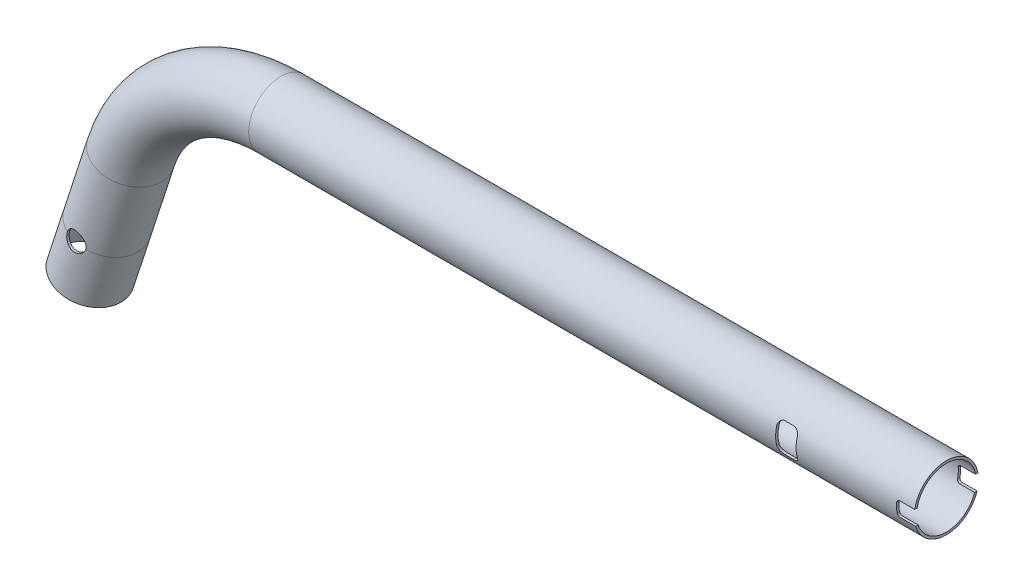
SolidWorks part; units mm, degrees
ref_plane "Front Plane" through (0, 0, 0) normal (0, 0, 1) x (1, 0, 0)
ref_plane "Top Plane" through (0, 0, 0) normal (0, 1, 0) x (1, 0, 0)
ref_plane "Right Plane" through (0, 0, 0) normal (1, 0, 0) x (0, 0, -1)
sketch "Sketch1" plane through (0, 0, 0) normal (0, 0, 1) x (1, 0, 0)
  line L0 (-91.9783, 0) -> (91.9783, 0)
  line L1 (-143.3354, -37.3131) -> (-151.4217, -62.2)
  line L2 (91.9783, 0) -> (135.9783, 0)
  line L3 (-151.4217, -62.2) -> (-157.2052, -80)
  arc A0 (-91.9783, 0) -> (-143.3354, -37.3131) centre (-91.9783, -54) ccw
  point P4 (0, 0)
  point P10 (-151.4217, -62.2)
  dimension "D2" = 54
  dimension "D1" = 72
  dimension "D3" = 62.2
  dimension "D4" = 243.4
  dimension "D5" = 80
  dimension "D6" = 72
  dimension "D7" = 44
ref_plane "Plane1" through (91.9783, 0, 0) normal (1, 0, 0) x (0, 0, -1)
sketch "Sketch3" plane through (91.9783, 0, 0) normal (1, 0, 0) x (0, 0, -1)
  circle A0 centre (0, 0) radius 11
  circle A1 centre (0, 0) radius 10.2
  dimension "D1" = 0.8
  dimension "D2" = 22
sweep "Sweep2" add profiles "Sketch3" path "Sketch1"
ref_axis "Axis1" through (135.9783, 0, 0) along (-1, 0, 0)
ref_axis "Axis2" through (-141.3374, -31.1639, 0) along (-0.309, -0.9511, 0)
sketch "Sketch4" plane through (0, 0, 0) normal (0, 0, 1) x (1, 0, 0)
  line L0 (-161.8833, -58.8008) -> (-140.96, -65.5992) construction
  line L1 (91.9783, -101.4635) -> (91.9783, 101.4635) construction
  line L2 (135.9783, 0) -> (91.9783, 0) construction
  line L3 (135.9783, -11) -> (135.9783, 11) construction
  line L4 (135.9783, 0) -> (-91.9783, 0) construction
  line L6 (90.4783, -5) -> (93.4783, -5)
  line L7 (88.4783, -3) -> (88.4783, 3)
  line L8 (90.4783, 5) -> (93.4783, 5)
  line L9 (95.4783, -3) -> (95.4783, 3)
  line L10 (88.4783, -5) -> (95.4783, 5) construction
  line L11 (88.4783, 5) -> (95.4783, -5) construction
  circle A0 centre (-151.4217, -62.2) radius 3.3
  arc A1 (90.4783, -5) -> (88.4783, -3) centre (90.4783, -3) cw
  arc A2 (95.4783, -3) -> (93.4783, -5) centre (93.4783, -3) cw
  arc A3 (93.4783, 5) -> (95.4783, 3) centre (93.4783, 3) cw
  arc A4 (90.4783, 5) -> (88.4783, 3) centre (90.4783, 3) ccw
  dimension "D1" = 44
  dimension "D4" = 2
  dimension "D6" = 6.6
  dimension "D2" = 7
  dimension "D3" = 10
extrude "Cut-Extrude1" cut sketch "Sketch4" along normal up to next
sketch "Sketch5" plane through (0, 0, 0) normal (0, 0, 1) x (1, 0, 0)
  line L0 (-161.1224, -59.048) -> (-141.7209, -65.352) construction
  circle A0 centre (-151.4217, -62.2) radius 3.3
extrude "Cut-Extrude2" cut sketch "Sketch5" against normal through all
sketch "Sketch6" plane through (0, 0, 0) normal (0, 0, 1) x (1, 0, 0)
  line L0 (135.9783, 1.95) -> (135.9783, -3.25)
  line L1 (135.9783, -11) -> (135.9783, 11) construction
  line L2 (135.9783, -3.25) -> (130.8783, -3.25)
  line L3 (129.8783, -2.25) -> (129.8783, 0.95)
  line L4 (130.8783, 1.95) -> (135.9783, 1.95)
  arc A0 (129.8783, -2.25) -> (130.8783, -3.25) centre (130.8783, -2.25) ccw
  arc A1 (130.8783, 1.95) -> (129.8783, 0.95) centre (130.8783, 0.95) ccw
  point P5 (135.9783, -0.65)
  point P9 (129.8783, -3.25)
  dimension "D3" = 1
  dimension "D1" = 5.2
  dimension "D2" = 6.1
extrude "Cut-Extrude3" cut sketch "Sketch6" against normal through all and the other way through all
